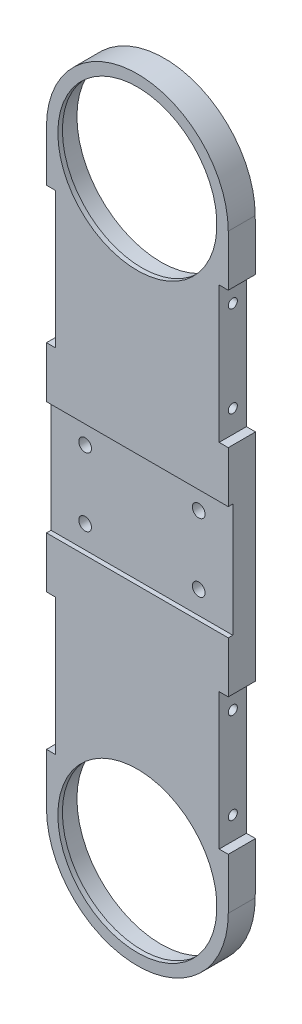
SolidWorks part; units mm, degrees
ref_plane "정면" through (0, 0, 0) normal (0, 0, 1) x (1, 0, 0)
ref_plane "윗면" through (0, 0, 0) normal (0, 1, 0) x (1, 0, 0)
ref_plane "우측면" through (0, 0, 0) normal (1, 0, 0) x (0, 0, -1)
sketch "스케치1" plane through (0, 0, 0) normal (0, 0, 1) x (1, 0, 0)
  line L2 (-20, 0) -> (-20, 130)
  line L4 (20, 0) -> (20, 130)
  arc A0 (-20, 0) -> (20, 0) centre (0, 0) ccw
  arc A1 (20, 130) -> (-20, 130) centre (0, 130) ccw
  dimension "D1" = 40
  dimension "D3" = 20
  dimension "D2" = 130
extrude "보스-돌출1" add sketch "스케치1" along normal blind 6
sketch "스케치2" plane through (0, 0, 0) normal (0, 0, -1) x (-1, 0, 0)
  circle A0 centre (0, 0) radius 18.5
  circle A1 centre (0, 130) radius 18.5
  dimension "D1" = 37
  dimension "D2" = 37
extrude "컷-돌출1" cut sketch "스케치2" against normal blind 5
chamfer "모따기1" distance 0.8 angle 64 2 edges at (-18.5, 130, 0) (-18.5, 0, 0) first distance on face at (-18.5, 130, 5) first distance on face at (-18.5, 0, 5)
sketch "스케치18" plane through (0, 0, 6) normal (0, 0, 1) x (1, 0, 0)
  line L0 (20, 0) -> (20, 130) construction
  line L1 (-20, 52.5) -> (20, 52.5)
  line L2 (-20, 52.5) -> (-20, 77.5)
  line L3 (-20, 77.5) -> (20, 77.5)
  line L4 (20, 52.5) -> (20, 77.5)
  line L5 (-20, 52.5) -> (20, 77.5) construction
  line L6 (-20, 77.5) -> (20, 52.5) construction
  arc A0 (20, 130) -> (-20, 130) centre (0, 130) ccw construction
  point P0 (0, 65)
  dimension "D1" = 25
  dimension "D2" = 52.5
extrude "컷-돌출9" cut sketch "스케치18" against normal blind 1
sketch "스케치19" plane through (0, 0, 5) normal (0, 0, 1) x (1, 0, 0)
  line L0 (-20, 65) -> (20, 65) construction
  line L3 (-20, 77.5) -> (-20, 52.5) construction
  line L4 (20, 52.5) -> (20, 77.5) construction
  line L6 (-12.5, 72.5) -> (12.5, 72.5) construction
  line L7 (-12.5, 72.5) -> (-12.5, 57.5) construction
  line L8 (-12.5, 57.5) -> (12.5, 57.5) construction
  line L9 (12.5, 72.5) -> (12.5, 57.5) construction
  line L10 (-12.5, 72.5) -> (12.5, 57.5) construction
  line L11 (-12.5, 57.5) -> (12.5, 72.5) construction
  circle A2 centre (-12.5, 72.5) radius 1.4
  circle A3 centre (12.5, 72.5) radius 1.4
  circle A4 centre (-12.5, 57.5) radius 1.4
  circle A5 centre (12.5, 57.5) radius 1.4
  point P6 (0, 65)
  dimension "D3" = 2.8
  dimension "D1" = 25
  dimension "D2" = 15
extrude "컷-돌출10" cut sketch "스케치19" against normal through all
sketch "스케치20" plane through (0, 0, 0) normal (0, 0, -1) x (-1, 0, 0)
  circle A0 centre (-12.5, 72.5) radius 2.25
  circle A1 centre (12.5, 72.5) radius 2.25
  circle A2 centre (-12.5, 57.5) radius 2.25
  circle A3 centre (12.5, 57.5) radius 2.25
  dimension "D1" = 4.5
extrude "컷-돌출11" cut sketch "스케치20" against normal blind 0.7
sketch "스케치21" plane through (0, 0, 6) normal (0, 0, 1) x (1, 0, 0)
  line L0 (-20, 130) -> (-20, 77.5) construction
  line L1 (-22, 118.75) -> (-18, 118.75)
  line L2 (-22, 118.75) -> (-22, 88.75)
  line L3 (-22, 88.75) -> (-18, 88.75)
  line L4 (-18, 118.75) -> (-18, 88.75)
  line L5 (-22, 118.75) -> (-18, 88.75) construction
  line L6 (-22, 88.75) -> (-18, 118.75) construction
  line L7 (20, 77.5) -> (20, 130) construction
  line L8 (22, 118.75) -> (18, 118.75)
  line L9 (22, 118.75) -> (22, 88.75)
  line L10 (22, 88.75) -> (18, 88.75)
  line L11 (18, 118.75) -> (18, 88.75)
  line L12 (22, 118.75) -> (18, 88.75) construction
  line L13 (22, 88.75) -> (18, 118.75) construction
  line L14 (-20, 52.5) -> (-20, 0) construction
  line L15 (-22, 11.25) -> (-18, 11.25)
  line L16 (-22, 11.25) -> (-22, 41.25)
  line L17 (-22, 41.25) -> (-18, 41.25)
  line L18 (-18, 11.25) -> (-18, 41.25)
  line L19 (-22, 11.25) -> (-18, 41.25) construction
  line L20 (-22, 41.25) -> (-18, 11.25) construction
  line L21 (20, 0) -> (20, 52.5) construction
  line L22 (22, 11.25) -> (18, 11.25)
  line L23 (22, 11.25) -> (22, 41.25)
  line L24 (22, 41.25) -> (18, 41.25)
  line L25 (18, 11.25) -> (18, 41.25)
  line L26 (22, 11.25) -> (18, 41.25) construction
  line L27 (22, 41.25) -> (18, 11.25) construction
  point P0 (-20, 103.75)
  point P7 (20, 103.75)
  point P14 (-20, 26.25)
  point P21 (20, 26.25)
  dimension "D1" = 4
  dimension "D2" = 30
extrude "컷-돌출12" cut sketch "스케치21" against normal through all
sketch "스케치22" plane through (18, 0, 0) normal (1, 0, 0) x (0, 0, -1)
  line L0 (-3, 118.75) -> (-3, 11.25) construction
  line L1 (0, 118.75) -> (-6, 118.75) construction
  line L2 (0, 11.25) -> (-6, 11.25) construction
  circle A0 centre (-3, 16.25) radius 1
  circle A1 centre (-3, 36.25) radius 1
  circle A2 centre (-3, 113.75) radius 1
  circle A3 centre (-3, 93.75) radius 1
  dimension "D1" = 20
  dimension "D2" = 2
  dimension "D3" = 5
  dimension "D4" = 20
  dimension "D5" = 5
extrude "컷-돌출13" cut sketch "스케치22" against normal blind 6
sketch "스케치23" plane through (-18, 0, 0) normal (-1, 0, 0) x (0, 0, 1)
  line L0 (3, 118.75) -> (3, 6.25) construction
  line L1 (0, 118.75) -> (6, 118.75) construction
  line L3 (0, 41.25) -> (6, 41.25) construction
  line L4 (0, 118.75) -> (6, 118.75) construction
  circle A0 centre (3, 16.25) radius 1
  circle A1 centre (3, 36.25) radius 1
  circle A2 centre (3, 113.75) radius 1
  circle A3 centre (3, 93.75) radius 1
  dimension "D1" = 2
  dimension "D2" = 20
  dimension "D3" = 5
  dimension "D4" = 20
  dimension "D5" = 5
extrude "컷-돌출14" cut sketch "스케치23" against normal blind 6
sketch "스케치24" plane through (0, 0, 5) normal (0, 0, -1) x (-1, 0, 0)
  circle A0 centre (0, 130) radius 17.5
  circle A1 centre (0, 0) radius 17.5
  circle A2 centre (0, 130) radius 18.5 construction
  circle A3 centre (0, 0) radius 18.5 construction
  dimension "D1" = 1
  dimension "D2" = 1
extrude "컷-돌출15" cut sketch "스케치24" against normal through all
